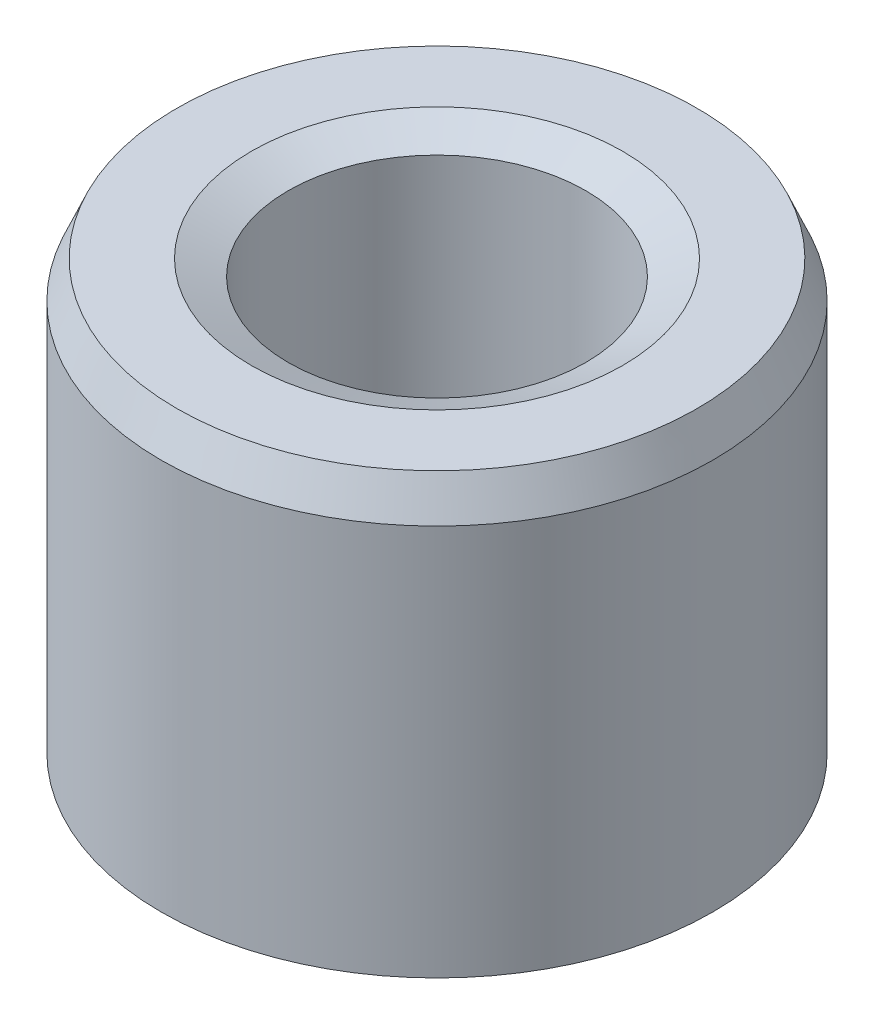
SolidWorks part; units mm, degrees
ref_plane "Front Plane" through (0, 0, 0) normal (0, 0, 1) x (1, 0, 0)
ref_plane "Top Plane" through (0, 0, 0) normal (0, 1, 0) x (1, 0, 0)
ref_plane "Right Plane" through (0, 0, 0) normal (1, 0, 0) x (0, 0, -1)
sketch "Sketch1" plane through (0, 0, 0) normal (0, 1, 0) x (1, 0, 0)
  circle A0 centre (0, 0) radius 22.5
  dimension "SLEEVE_OD" = 45
extrude "Boss-Extrude1" add sketch "Sketch1" along normal blind 36.2004
sketch "Sketch2" plane through (0, 0, 0) normal (0, 1, 0) x (1, 0, 0)
  circle A0 centre (0, 0) radius 12.1387
  dimension "BORE_D" = 24.2773
extrude "Cut-Extrude1" cut sketch "Sketch2" along normal through all
chamfer "Chamfer1" distance 3.0013 angle 23.165 4 edges at (0, 36.2004, 12.1387) (0, 0, 12.1387) (0, 0, 22.5) (0, 36.2004, 22.5) first distance on face at (0, 36.2004, 12.1387) first distance on face at (0, 0, 12.1387) first distance on face at (0, 36.2004, 22.5)
